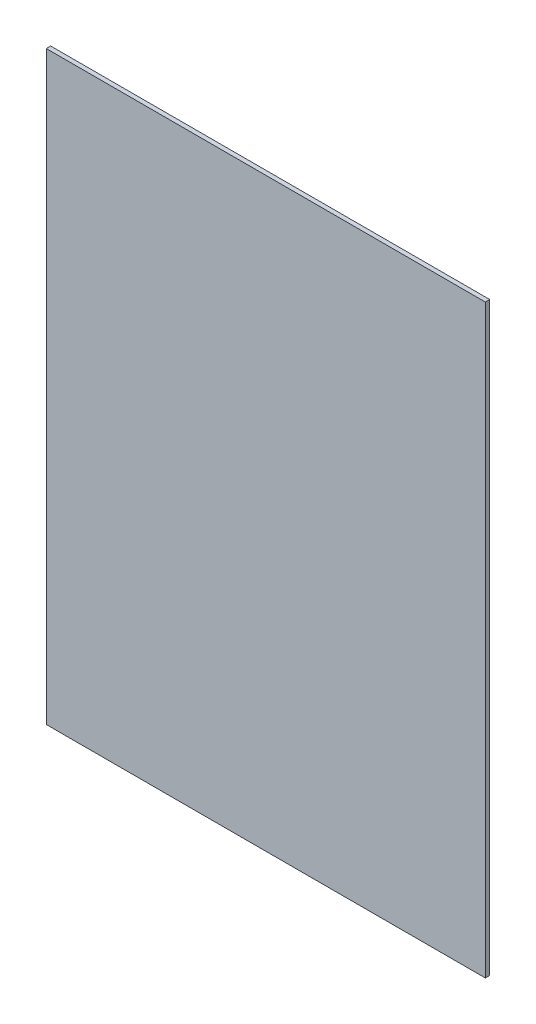
SolidWorks part; units mm, degrees
ref_plane "Plano frontal" through (0, 0, 0) normal (0, 0, 1) x (1, 0, 0)
ref_plane "Plano superior" through (0, 0, 0) normal (0, 1, 0) x (1, 0, 0)
ref_plane "Plano direito" through (0, 0, 0) normal (1, 0, 0) x (0, 0, -1)
sketch "Esboço1" plane through (0, 0, 0) normal (0, 0, 1) x (1, 0, 0)
  line L1 (-150, -200) -> (150, -200)
  line L2 (-150, -200) -> (-150, 200)
  line L3 (-150, 200) -> (150, 200)
  line L4 (150, -200) -> (150, 200)
  line L5 (-150, -200) -> (150, 200) construction
  line L6 (-150, 200) -> (150, -200) construction
  point P0 (0, 0)
  dimension "D1" = 400
  dimension "D2" = 300
extrude "Ressalto-extrusão1" add sketch "Esboço1" along normal blind 3
